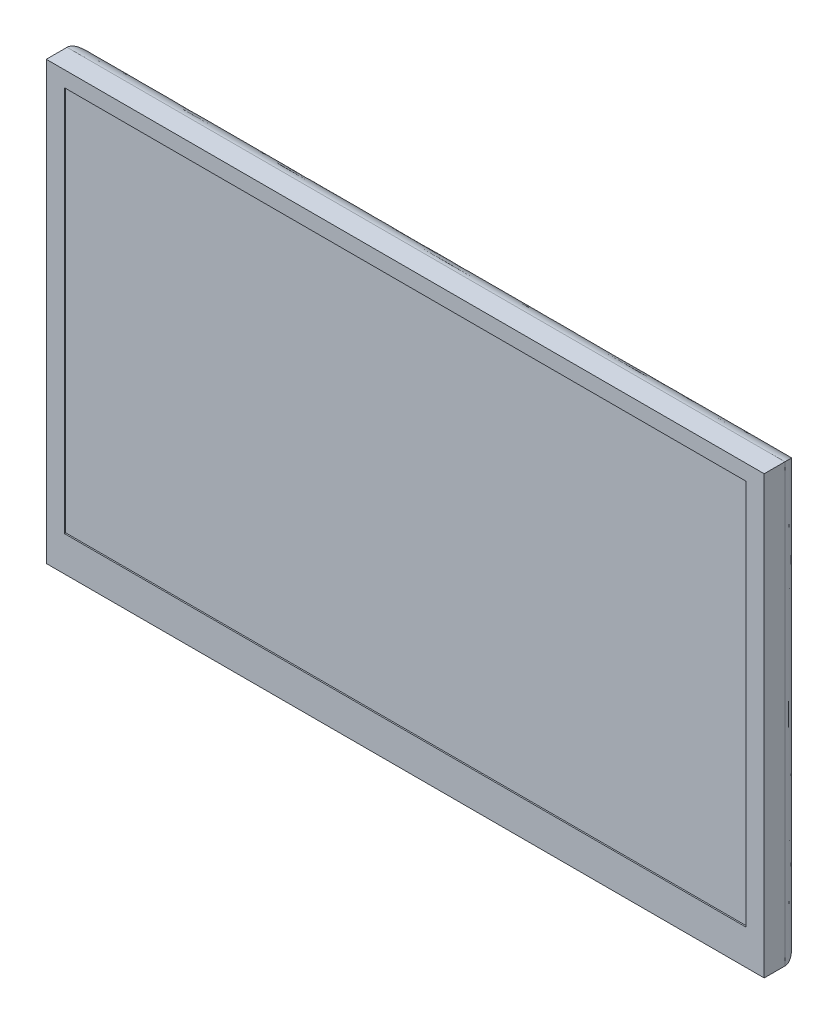
SolidWorks part; units mm, degrees
ref_plane "Спереди" through (0, 0, 0) normal (0, 0, 1) x (1, 0, 0)
ref_plane "Сверху" through (0, 0, 0) normal (0, 1, 0) x (1, 0, 0)
ref_plane "Справа" through (0, 0, 0) normal (1, 0, 0) x (0, 0, -1)
sketch "Эскиз1" plane through (0, 0, 0) normal (0, 0, 1) x (1, 0, 0)
  line L1 (-56.6364, 26.4202) -> (497.3636, 26.4202)
  line L2 (-56.6364, 26.4202) -> (-56.6364, -310.5798)
  line L3 (-56.6364, -310.5798) -> (497.3636, -310.5798)
  line L4 (497.3636, 26.4202) -> (497.3636, -310.5798)
  dimension "D1" = 554
  dimension "D2" = 337
extrude "Бобышка-Вытянуть1" add sketch "Эскиз1" against normal blind 56
fillet "Скругление1" radius 150 4 edges at (220.3636, -310.5798, -56) (-56.6364, -142.0798, -56) (220.3636, 26.4202, -56) (497.3636, -142.0798, -56) second distance 40 first distance on face at (220.3636, -142.0798, -56)
sketch "Эскиз2" plane through (0, 0, 0) normal (0, 0, 1) x (1, 0, 0)
  line L0 (497.3636, 26.4202) -> (-56.6364, 26.4202) construction
  line L1 (-42.6364, 14.4202) -> (483.3636, 14.4202)
  line L2 (-42.6364, 14.4202) -> (-42.6364, -283.5798)
  line L3 (-42.6364, -283.5798) -> (483.3636, -283.5798)
  line L4 (483.3636, 14.4202) -> (483.3636, -283.5798)
  line L5 (220.3636, -310.5798) -> (220.3636, 36.5669) construction
  line L6 (-56.6364, -310.5798) -> (497.3636, -310.5798) construction
  point P10 (220.3636, 14.4202)
  dimension "D1" = 526
  dimension "D2" = 298
  dimension "D3" = 12
extrude "Вырез-Вытянуть1" cut sketch "Эскиз2" against normal blind 1
sketch "Эскиз3" plane through (0, -310.5798, 0) normal (0, -1, 0) x (1, 0, 0)
  line L1 (372.3636, -4.1987) -> (462.3636, -4.1987)
  line L2 (372.3636, -4.1987) -> (372.3636, -12.0837)
  line L3 (372.3636, -12.0837) -> (462.3636, -12.0837)
  line L4 (462.3636, -4.1987) -> (462.3636, -12.0837)
  line L5 (497.3636, -16) -> (497.3636, 0) construction
  dimension "D1" = 90
  dimension "D2" = 35
extrude "Бобышка-Вытянуть2" add sketch "Эскиз3" along normal blind 3
sketch3d "Трехмерный эскиз1"
  line L0 (220.3636, -310.5798, 0) -> (220.3636, 26.4202, 0) construction
  line L1 (-56.6364, -310.5798, 0) -> (497.3636, -310.5798, 0) construction
  line L2 (497.3636, 26.4202, 0) -> (-56.6364, 26.4202, 0) construction
ref_plane "Плоскость1" through (220.3636, 0, 0) normal (-1, 0, 0) x (0, 0, 1)
